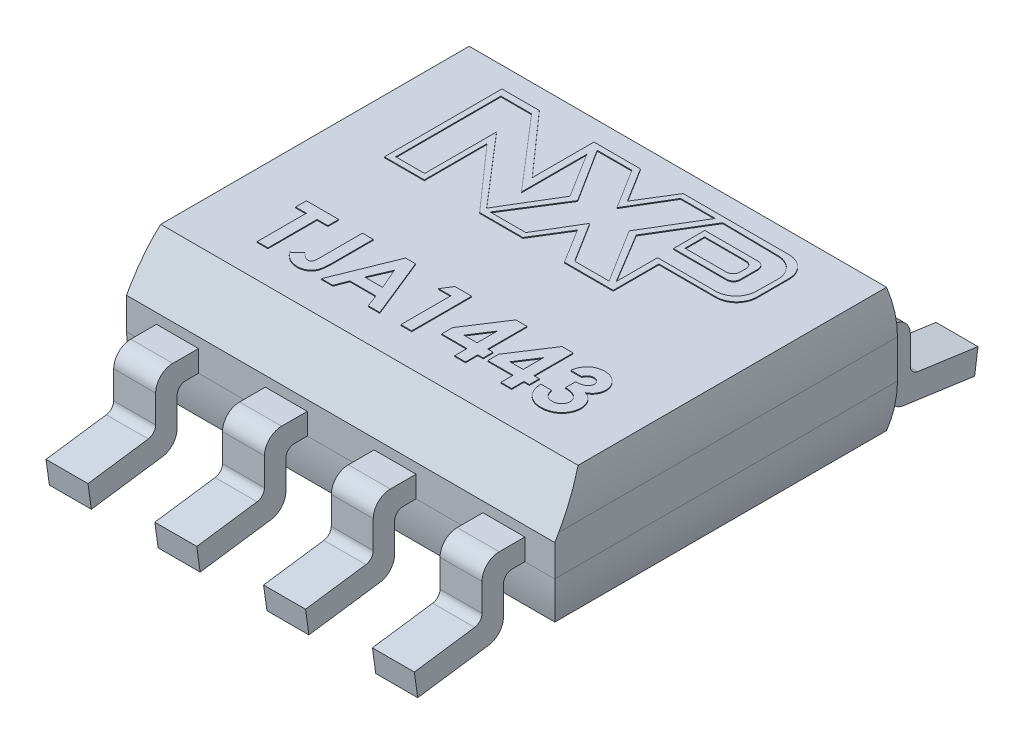
SolidWorks part; units mm, degrees
ref_plane "Front Plane" through (0, 0, 0) normal (0, 0, 1) x (1, 0, 0)
ref_plane "Top Plane" through (0, 0, 0) normal (0, 1, 0) x (1, 0, 0)
ref_plane "Right Plane" through (0, 0, 0) normal (1, 0, 0) x (0, 0, -1)
sketch "Sketch1" plane through (0, 0, 0) normal (0, 1, 0) x (1, 0, 0)
  line L1 (-2.5, 2) -> (2.5, 2)
  line L2 (-2.5, 2) -> (-2.5, -2)
  line L3 (-2.5, -2) -> (2.5, -2)
  line L4 (2.5, 2) -> (2.5, -2)
  line L5 (-2.5, 2) -> (2.5, -2) construction
  line L6 (-2.5, -2) -> (2.5, 2) construction
  point P0 (0, 0)
  dimension "D1" = 5
  dimension "D2" = 4
extrude "Boss-Extrude1" add sketch "Sketch1" along normal blind 1.45
sketch "Sketch2" plane through (-2.5, 0, 0) normal (-1, 0, 0) x (0, 0, 1)
  line L0 (2, 0.8687) -> (1.6644, 1.45)
  line L1 (2, 1.45) -> (2, 0) construction
  line L2 (-2, 1.45) -> (2, 1.45) construction
  line L3 (0, 0) -> (0, 0.828) construction
  line L4 (-2, 0.725) -> (-1.3983, 0.725) construction
  line L6 (-2, 1.45) -> (-2, 0) construction
  line L7 (-1.8644, 1.6723) -> (-2.1559, 1.6723)
  line L8 (-2.1559, 1.6723) -> (-2.1559, 0.954)
  line L9 (-2.1559, 0.954) -> (-2, 0.9484)
  line L10 (-2, 0.5016) -> (-2.1559, 0.5016)
  line L11 (-2.1559, 0.5016) -> (-2.1559, -0.2223)
  line L12 (-2.1559, -0.2223) -> (-1.8644, -0.2223)
  line L13 (1.6644, 1.45) -> (1.6644, 1.7317)
  line L14 (1.6644, 1.7317) -> (2.4871, 1.7317)
  line L15 (2.4871, 1.7317) -> (2.4871, 0.8687)
  line L16 (2.4871, 0.8687) -> (2, 0.8687)
  line L17 (2, 0.5015) -> (2.4871, 0.5015)
  line L18 (2.4871, 0.5015) -> (2.4871, -0.2223)
  line L19 (2.4871, -0.2223) -> (1.8644, -0.2223)
  arc A0 (2, 0.5015) -> (1.8644, -0.2223) centre (0, 0.5015) cw
  arc A1 (-2, 0.5016) -> (-1.8644, -0.2223) centre (0, 0.5015) ccw
  arc A2 (-2, 0.9484) -> (-1.8644, 1.6723) centre (0, 0.9485) cw
  dimension "D1" = 2
  dimension "D2" = 60
extrude "Cut-Extrude1" cut sketch "Sketch2" against normal blind 61.45
sketch "Sketch5" plane through (0, 0, -2) normal (0, 0, -1) x (-1, 0, 0)
  line L1 (0, 1.45) -> (0, 1.0867) construction
  line L2 (-3.4587, 0.725) -> (-2.857, 0.725) construction
  line L3 (-2.3644, 1.6723) -> (-2.6559, 1.6723)
  line L4 (-2.6559, 1.6723) -> (-2.6559, 0.954)
  line L5 (-2.6559, 0.954) -> (-2.5, 0.9484)
  line L6 (-2.5, 0.5016) -> (-2.6559, 0.5016)
  line L7 (-2.6559, 0.5016) -> (-2.6559, -0.2223)
  line L8 (-2.6559, -0.2223) -> (-2.3644, -0.2223)
  line L16 (2.5, 1.45) -> (-2.5, 1.45) construction
  line L17 (-2.6559, 1.6723) -> (-2.3644, 1.6723)
  line L18 (-2.6559, 0.9484) -> (-2.6559, 1.6723)
  line L19 (-2.5, 0.9484) -> (-2.6559, 0.9484)
  line L20 (-2.6559, 0.496) -> (-2.5, 0.5016)
  line L21 (-2.6559, -0.2223) -> (-2.6559, 0.496)
  line L22 (-2.3644, -0.2223) -> (-2.6559, -0.2223)
  line L23 (2.6559, -0.2223) -> (2.3644, -0.2223)
  line L24 (2.6559, 0.5016) -> (2.6559, -0.2223)
  line L25 (2.5, 0.5016) -> (2.6559, 0.5016)
  line L26 (2.6559, 0.954) -> (2.5, 0.9484)
  line L27 (2.6559, 1.6723) -> (2.6559, 0.954)
  line L28 (2.3644, 1.6723) -> (2.6559, 1.6723)
  arc A1 (-2.5, 0.5016) -> (-2.3644, -0.2223) centre (-0.5, 0.5015) ccw
  arc A2 (-2.5, 0.9484) -> (-2.3644, 1.6723) centre (-0.5, 0.9485) cw
  arc A3 (-2.5, 0.5016) -> (-2.3644, -0.2223) centre (-0.5, 0.5015) ccw
  arc A4 (-2.5, 0.9484) -> (-2.3644, 1.6723) centre (-0.5, 0.9485) cw
  arc A5 (2.5, 0.5016) -> (2.3644, -0.2223) centre (0.5, 0.5015) cw
  arc A6 (2.5, 0.9484) -> (2.3644, 1.6723) centre (0.5, 0.9485) ccw
extrude "Cut-Extrude2" cut sketch "Sketch5" against normal blind 61.45 contours L5 A2 L3 L4 | A1 L20 L7 L22 | A6 L26 L27 L28 | L25 A5 L23 L24
sketch "Sketch6" plane through (-2.5, 0, 0) normal (-1, 0, 0) x (0, 0, 1)
  line L5 (1.9361, 0) -> (-1.9361, 0) construction
  line L7 (0, 0) -> (0, -0.7239) construction
  line L8 (2.2535, 0.75) -> (2.3, 0.75)
  line L9 (2.5, 0.55) -> (2.5, 0.2276)
  line L10 (2.5, 0.1406) -> (3.25, 0.1406) construction
  line L11 (3.25, 0.1406) -> (3.25, -0.1094) construction
  line L12 (3.25, -0.1094) -> (2.25, -0.1094) construction
  line L13 (2.25, 0.0645) -> (2.25, 0.4)
  line L14 (2.25, 0.5) -> (2.2535, 0.5)
  line L15 (-3.25, -0.1094) -> (-2.25, -0.1094) construction
  line L17 (2.4222, -0.1335) -> (3.2508, -0.25)
  line L18 (2.5861, 0.1286) -> (3.2901, 0.0296)
  line L19 (3.2508, -0.25) -> (3.2901, 0.0296)
  line L20 (-3.25, 0.1406) -> (-3.25, -0.1094) construction
  line L21 (-2.5, 0.1406) -> (-3.25, 0.1406) construction
  line L22 (-3.2508, -0.25) -> (-3.2901, 0.0296)
  line L23 (-2.5861, 0.1286) -> (-3.2901, 0.0296)
  line L24 (-2.4222, -0.1335) -> (-3.2508, -0.25)
  line L25 (-2.25, 0.5) -> (-2.2535, 0.5)
  line L26 (-2.25, 0.0645) -> (-2.25, 0.4)
  line L27 (-2.5, 0.55) -> (-2.5, 0.2276)
  line L28 (-2.2535, 0.75) -> (-2.3, 0.75)
  line L29 (-2.15, 0.5) -> (2.15, 0.5)
  line L30 (-2.2535, 0.75) -> (2.2535, 0.75)
  arc A0 (2.4222, -0.1335) -> (2.25, 0.0645) centre (2.45, 0.0645) cw
  arc A1 (2.5, 0.55) -> (2.3, 0.75) centre (2.3, 0.55) ccw
  arc A2 (2.5861, 0.1286) -> (2.5, 0.2276) centre (2.6, 0.2276) cw
  arc A3 (2.25, 0.4) -> (2.15, 0.5) centre (2.15, 0.4) ccw
  arc A4 (-2.25, 0.4) -> (-2.15, 0.5) centre (-2.15, 0.4) cw
  arc A5 (-2.5861, 0.1286) -> (-2.5, 0.2276) centre (-2.6, 0.2276) ccw
  arc A6 (-2.5, 0.55) -> (-2.3, 0.75) centre (-2.3, 0.55) cw
  arc A7 (-2.4222, -0.1335) -> (-2.25, 0.0645) centre (-2.45, 0.0645) ccw
  dimension "D9" = 0.2
  dimension "D10" = 0.1
  dimension "D4" = 0.25
  dimension "D5" = 0.25
  dimension "D6" = 1
  dimension "D7" = 8
  dimension "D8" = 0.25
extrude "Boss-Extrude2" add sketch "Sketch6" against normal up to surface (5 mm away) up to face at (2.5, 0.8431, 0.3908)
sketch "Sketch7" plane through (0, 1.45, 0) normal (0, 1, 0) x (1, 0, 0)
  line L0 (2.5, -2) -> (-2.5, -2) construction
  line L1 (-2.5, -2) -> (-2.15, -2)
  line L2 (-2.5, -2) -> (-2.5, -3.534)
  line L3 (-2.5, -3.534) -> (-2.15, -3.534)
  line L4 (-2.15, -2) -> (-2.15, -3.534)
  line L5 (-1.66, -2) -> (-0.88, -2)
  line L6 (-1.66, -2) -> (-1.66, -3.6106)
  line L7 (-1.66, -3.6106) -> (-0.88, -3.6106)
  line L8 (-0.88, -2) -> (-0.88, -3.6106)
  line L9 (0, 0) -> (-3.4858, 0) construction
  line L10 (-0.39, -2) -> (0.39, -2)
  line L11 (-0.39, -2) -> (-0.39, -3.6106)
  line L12 (-0.39, -3.6106) -> (0.39, -3.6106)
  line L13 (0.39, -2) -> (0.39, -3.6106)
  line L14 (2.5, -2) -> (2.15, -2)
  line L15 (2.5, -2) -> (2.5, -3.783)
  line L16 (2.5, -3.783) -> (2.15, -3.783)
  line L17 (2.15, -2) -> (2.15, -3.783)
  line L18 (1.66, -2) -> (0.88, -2)
  line L19 (1.66, -2) -> (1.66, -3.6776)
  line L20 (1.66, -3.6776) -> (0.88, -3.6776)
  line L21 (0.88, -2) -> (0.88, -3.6776)
  line L22 (0.88, 2) -> (0.88, 3.6776)
  line L23 (1.66, 3.6776) -> (0.88, 3.6776)
  line L24 (1.66, 2) -> (1.66, 3.6776)
  line L25 (1.66, 2) -> (0.88, 2)
  line L26 (2.15, 2) -> (2.15, 3.783)
  line L27 (2.5, 3.783) -> (2.15, 3.783)
  line L28 (2.5, 2) -> (2.5, 3.783)
  line L29 (2.5, 2) -> (2.15, 2)
  line L30 (0.39, 2) -> (0.39, 3.6106)
  line L31 (-0.39, 3.6106) -> (0.39, 3.6106)
  line L32 (-0.39, 2) -> (-0.39, 3.6106)
  line L33 (-0.39, 2) -> (0.39, 2)
  line L34 (-0.88, 2) -> (-0.88, 3.6106)
  line L35 (-1.66, 3.6106) -> (-0.88, 3.6106)
  line L36 (-1.66, 2) -> (-1.66, 3.6106)
  line L37 (-1.66, 2) -> (-0.88, 2)
  line L38 (-2.15, 2) -> (-2.15, 3.534)
  line L39 (-2.5, 3.534) -> (-2.15, 3.534)
  line L40 (-2.5, 2) -> (-2.5, 3.534)
  line L41 (-2.5, 2) -> (-2.15, 2)
  dimension "D1" = 0.49
  dimension "D2" = 0.49
  dimension "D3" = 0.49
  dimension "D4" = 0.49
  dimension "D5" = 0.78
  dimension "D6" = 0.78
  dimension "D7" = 0.78
  dimension "D8" = 0.35
extrude "Cut-Extrude3" cut sketch "Sketch7" against normal blind 61.45
sketch "Sketch8" plane through (0, 1.45, 0) normal (0, 1, 0) x (1, 0, 0)
  line L0 (70.6653, 255.7964) -> (518.6653, 255.7964) construction
  line L1 (-1.8034, 0.3139) -> (-1.8034, 1.6861)
  line L2 (-1.8034, 1.6861) -> (-1.3672, 1.6861)
  line L3 (-1.3672, 1.6861) -> (-0.7295, 0.965)
  line L4 (-0.7295, 0.965) -> (-0.7295, 1.6861)
  line L5 (-0.7295, 1.6861) -> (-0.186, 1.6861)
  line L6 (-0.186, 1.6861) -> (0.0636, 1.2836)
  line L7 (0.0636, 1.2836) -> (0.3123, 1.6861)
  line L8 (0.3123, 1.6861) -> (1.5487, 1.6861)
  line L9 (1.7887, 1.4461) -> (1.7887, 1.0732)
  line L10 (1.5487, 0.8332) -> (0.8817, 0.8332)
  line L11 (0.8817, 0.8332) -> (0.8817, 0.2999)
  line L12 (0.8817, 0.2999) -> (0.3123, 0.2999)
  line L13 (0.3123, 0.2999) -> (0.0636, 0.7007)
  line L14 (0.0636, 0.7007) -> (-0.1796, 0.3069)
  line L15 (-0.1796, 0.3069) -> (-0.6842, 0.3069)
  line L16 (-0.6842, 0.3069) -> (-1.3377, 1.046)
  line L17 (-1.3377, 1.046) -> (-1.3377, 0.3139)
  line L18 (-1.3377, 0.3139) -> (-1.8034, 0.3139)
  line L19 (-1.7377, 0.3801) -> (-1.7377, 1.6079)
  line L20 (-1.7377, 1.6079) -> (-1.3789, 1.6079)
  line L21 (-1.3789, 1.6079) -> (-0.6481, 0.759)
  line L22 (-0.6481, 0.759) -> (-0.6481, 1.5221)
  line L23 (-0.6481, 1.5221) -> (-0.3221, 0.9996)
  line L24 (-0.3221, 0.9996) -> (-0.6875, 0.3914)
  line L25 (-0.6875, 0.3914) -> (-1.3999, 1.219)
  line L26 (-1.3999, 1.219) -> (-1.3999, 0.3801)
  line L27 (-1.3999, 0.3801) -> (-1.7377, 0.3801)
  line L28 (-0.6279, 1.6222) -> (-0.2222, 1.6222)
  line L29 (-0.2222, 1.6222) -> (0.068, 1.1578)
  line L30 (0.068, 1.1578) -> (0.3464, 1.6222)
  line L31 (0.3464, 1.6222) -> (0.7514, 1.6222)
  line L32 (0.7514, 1.6222) -> (0.3743, 0.9932)
  line L33 (0.3743, 0.9932) -> (0.7643, 0.369)
  line L34 (0.7643, 0.369) -> (0.3619, 0.369)
  line L35 (0.3619, 0.369) -> (0.068, 0.8394)
  line L36 (0.068, 0.8394) -> (-0.2117, 0.373)
  line L37 (-0.2117, 0.373) -> (-0.6279, 0.373)
  line L38 (-0.6279, 0.373) -> (-0.2334, 0.9996)
  line L39 (-0.2334, 0.9996) -> (-0.6279, 1.6222)
  line L40 (0.8381, 1.6222) -> (1.4939, 1.613)
  line L41 (1.7305, 1.3696) -> (1.727, 1.1248)
  line L42 (1.4871, 0.8882) -> (0.8112, 0.8882)
  line L43 (0.8112, 0.8882) -> (0.8112, 0.4059)
  line L44 (0.8112, 0.4059) -> (0.4571, 0.9932)
  line L45 (0.4571, 0.9932) -> (0.8381, 1.6222)
  line L46 (0.8112, 1.4396) -> (1.433, 1.4396)
  line L47 (1.513, 1.3596) -> (1.513, 1.1532)
  line L48 (1.433, 1.0732) -> (0.8112, 1.0732)
  line L49 (0.8112, 1.4396) -> (0.8112, 1.0732)
  line L50 (0.8755, 1.3732) -> (1.3583, 1.3732)
  line L51 (0.8755, 1.3732) -> (0.8755, 1.144)
  line L52 (0.8755, 1.144) -> (1.3583, 1.144)
  line L53 (1.4383, 1.2932) -> (1.4383, 1.224)
  arc A0 (1.7887, 1.0732) -> (1.5487, 0.8332) centre (1.5487, 1.0732) cw
  arc A1 (1.5487, 1.6861) -> (1.7887, 1.4461) centre (1.5487, 1.4461) cw
  arc A2 (1.727, 1.1248) -> (1.4871, 0.8882) centre (1.4871, 1.1282) cw
  arc A3 (1.4939, 1.613) -> (1.7305, 1.3696) centre (1.4905, 1.373) cw
  arc A4 (1.3583, 1.144) -> (1.4383, 1.224) centre (1.3583, 1.224) ccw
  arc A5 (1.3583, 1.3732) -> (1.4383, 1.2932) centre (1.3583, 1.2932) cw
  arc A6 (1.513, 1.1532) -> (1.433, 1.0732) centre (1.433, 1.1532) cw
  arc A7 (1.433, 1.4396) -> (1.513, 1.3596) centre (1.433, 1.3596) cw
extrude "Boss-Extrude3" add sketch "Sketch8" along normal blind 0.01 contours A1 L8 L7 L6 L5 L4 L3 L2 L1 L18 L17 L16 L15 L14 L13 L12 L11 L10 A0 L9 L38 L39 L28 L29 L30 L31 L32 L33 L34 L35 L36 L37 L26 L27 L19 L20 L21 L22 L23 L24 L25 L40 A3 L41 A2 L42 L43 L44 | A7 L46 L49 L48 A6 L47 L50 A5 L53 A4 L52 L51
sketch "Sketch9" plane through (0, 1.45, 0) normal (0, 1, 0) x (1, 0, 0)
  line L0 (-1.8233, -1.2861) -> (2.2013, -1.2861) construction
  text T0 "<b>TJA1443</b>" font "Century Gothic" height 0.7
extrude "Boss-Extrude4" add sketch "Sketch9" along normal blind 0.01
